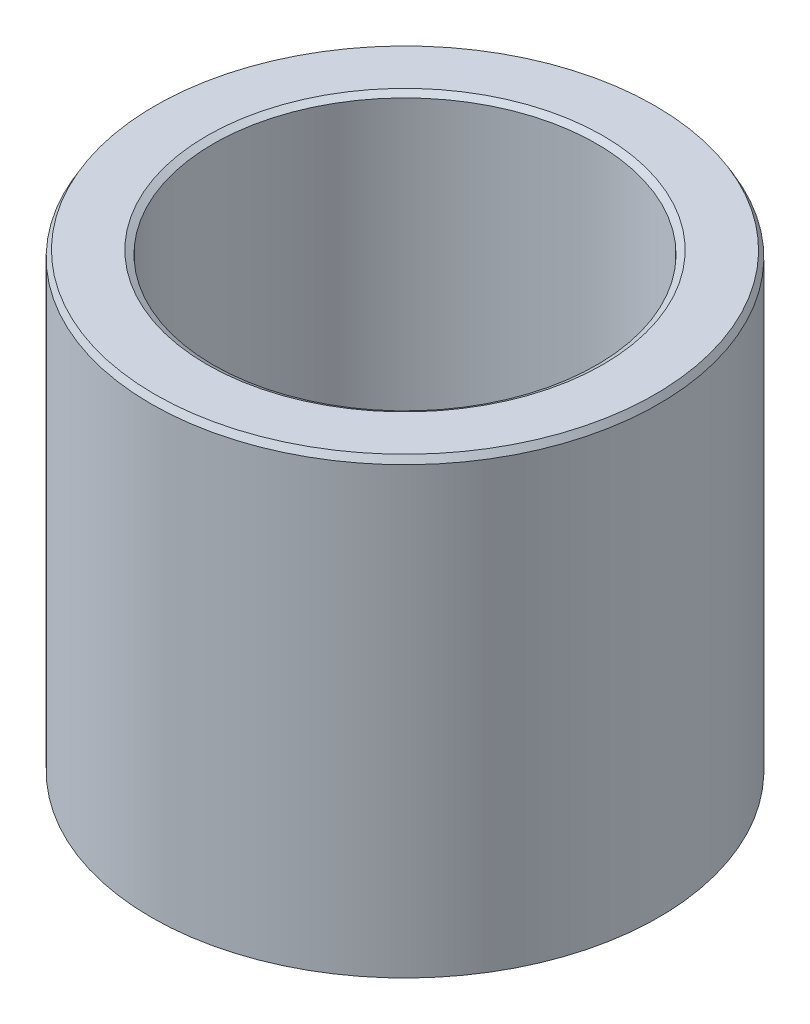
SolidWorks part; units mm, degrees
ref_plane "Front Plane" through (0, 0, 0) normal (0, 0, 1) x (1, 0, 0)
ref_plane "Top Plane" through (0, 0, 0) normal (0, 1, 0) x (1, 0, 0)
ref_plane "Right Plane" through (0, 0, 0) normal (1, 0, 0) x (0, 0, -1)
sketch "Sketch1" plane through (0, 0, 0) normal (0, 1, 0) x (1, 0, 0)
  circle A0 centre (0, 0) radius 40
  dimension "SLEEVE_OD" = 80
extrude "Boss-Extrude1" add sketch "Sketch1" along normal blind 71.6781
sketch "Sketch2" plane through (0, 0, 0) normal (0, 1, 0) x (1, 0, 0)
  circle A0 centre (0, 0) radius 30.2152
  dimension "BORE_D" = 60.4304
extrude "Cut-Extrude1" cut sketch "Sketch2" along normal through all
chamfer "Chamfer1" distance 1.0152 angle 30 4 edges at (0, 71.6781, 30.2152) (0, 0, 30.2152) (0, 0, 40) (0, 71.6781, 40) first distance on face at (0, 71.6781, 30.2152) first distance on face at (0, 0, 30.2152) first distance on face at (0, 71.6781, 40)
